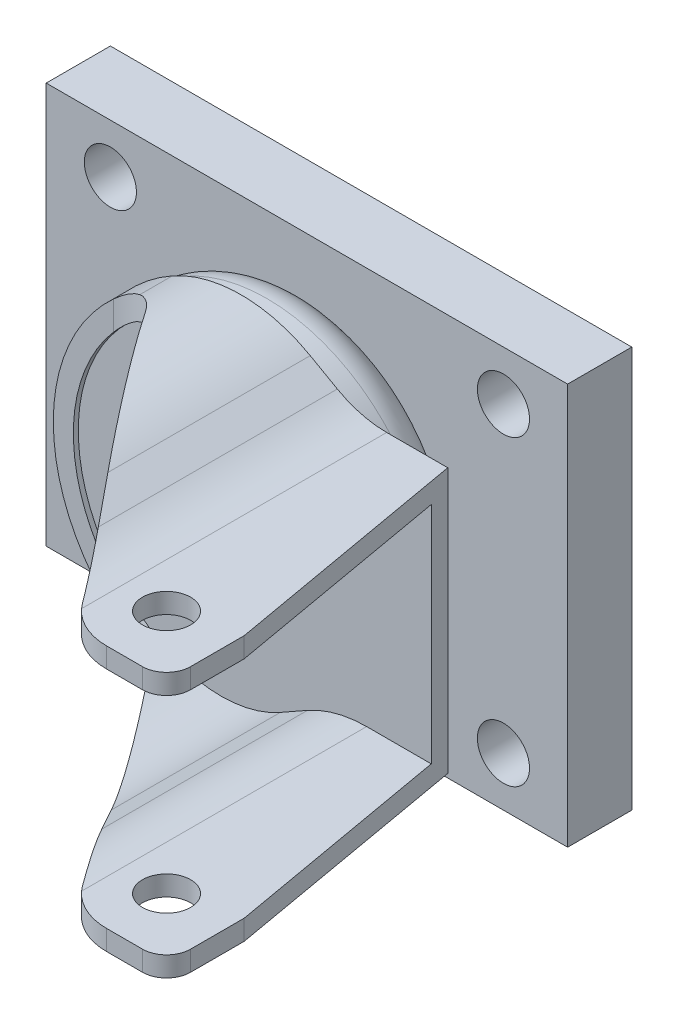
SolidWorks part; units mm, degrees
ref_plane "前视基准面" through (0, 0, 0) normal (0, 0, 1) x (1, 0, 0)
ref_plane "上视基准面" through (0, 0, 0) normal (0, 1, 0) x (1, 0, 0)
ref_plane "右视基准面" through (0, 0, 0) normal (1, 0, 0) x (0, 0, -1)
sketch "草图1" plane through (0, 0, 0) normal (0, 0, 1) x (1, 0, 0)
  line L0 (35.9458, 14) -> (49, 14)
  line L1 (35.9458, -14) -> (49, -14)
  line L2 (25.1846, 17.8522) -> (28.5649, 15.9416)
  line L3 (49, 14) -> (49, -14)
  line L4 (35.9458, -14) -> (49, -14)
  line L5 (25.1846, -17.8522) -> (28.5649, -15.9416)
  line L6 (35.9458, 14) -> (46.0599, 14)
  line L7 (35.9458, -14) -> (46.0599, -14)
  line L8 (35.9458, 14) -> (49, 14)
  line L9 (35.9458, -14) -> (49, -14)
  line L10 (25.1846, 17.8522) -> (28.5649, 15.9416)
  line L11 (49, 14) -> (49, -14)
  line L12 (35.9458, -14) -> (49, -14)
  line L13 (25.1846, -17.8522) -> (28.5649, -15.9416)
  line L14 (35.9458, 14) -> (46.0599, 14)
  line L15 (35.9458, -14) -> (46.0599, -14)
  arc A0 (10.4502, 17.8676) -> (10.4502, -17.8676) centre (20.5, 0) ccw
  arc A1 (25.1846, 17.8522) -> (10.4502, 17.8676) centre (17.8037, 4.7938) ccw
  arc A2 (28.5649, 15.9416) -> (35.9458, 14) centre (35.9458, 29) ccw
  arc A3 (10.4502, -17.8676) -> (25.1846, -17.8522) centre (17.8037, -4.7938) ccw
  arc A4 (35.9458, -14) -> (28.5649, -15.9416) centre (35.9458, -29) ccw
  arc A5 (10.4502, 17.8676) -> (10.4502, -17.8676) centre (20.5, 0) ccw
  arc A6 (25.1846, 17.8522) -> (10.4502, 17.8676) centre (17.8037, 4.7938) ccw
  arc A7 (28.5649, 15.9416) -> (35.9458, 14) centre (35.9458, 29) ccw
  arc A8 (10.4502, -17.8676) -> (25.1846, -17.8522) centre (17.8037, -4.7938) ccw
  arc A9 (35.9458, -14) -> (28.5649, -15.9416) centre (35.9458, -29) ccw
extrude "凸台-拉伸1" add sketch "草图1" along normal blind 46.5 contours A4 L1 L4 L3 L0 A2 L2 A1 A0 A3 L5 region at (24.4054, 0, 0)
sketch "草图4" plane through (0, -14, 0) normal (0, -1, 0) x (1, 0, 0)
  line L0 (49, 36.8137) -> (44, 8.5)
  line L1 (0, 8.5) -> (0, 9.114)
  line L2 (0, 9.114) -> (5, 9.114)
  line L3 (35.4725, 43.4631) -> (13.0367, 13.1632)
  line L4 (0, 8.5) -> (44, 8.5)
  line L5 (0, 46.5) -> (0, 0) construction
  line L6 (41.5, 46.5) -> (49, 46.5)
  line L7 (49, 46.5) -> (49, 0) construction
  line L8 (35.9458, 46.5) -> (49, 46.5) construction
  line L9 (49, 46.5) -> (49, 36.8137)
  arc A0 (41.5, 46.5) -> (35.4725, 43.4631) centre (41.5, 39) ccw
  arc A1 (13.0367, 13.1632) -> (5, 9.114) centre (5, 19.114) cw
  circle A4 centre (41.5, 39) radius 3
  dimension "D1" = 38
  dimension "D2" = 30.5
  dimension "D5" = 6
  dimension "D6" = 10
  dimension "D3" = 5
extrude "切除-拉伸1" cut sketch "草图4" against normal mid plane 100 flip side to cut contours L4 L0 L9 L6 A0 L3 A1 L2 L1
shell "抽壳1" thickness 2.5 removed face at (49, 0, 41.6568) removed face at (37.5527, 0.0012, 44.8635) removed face at (25.5663, 0, 30.0846) removed face at (9.5473, -0.1903, 10.8419) removed face at (2.5, 0, 9.114) removed face at (45.25, 0, 46.5) removed face at (46.5, 0, 22.6568) outward yes
sketch "草图5" plane through (0, 0, 6) normal (0, 0, -1) x (-1, 0, 0)
  line L0 (2.5, 0) -> (-49, 0) construction
  line L1 (-49, 14) -> (-49, -14) construction
  circle A0 centre (-18, 0) radius 20.5
  dimension "D1" = 41
extrude "凸台-拉伸3" add sketch "草图5" along normal blind 8
fillet "圆角1" radius 5 1 edges at (-2.5, 0, -2)
sketch "草图7" plane through (0, 0, -2) normal (0, 0, -1) x (-1, 0, 0)
  line L1 (-10, 0) -> (-14, 6.9282)
  line L2 (-14, 6.9282) -> (-22, 6.9282)
  line L3 (-22, 6.9282) -> (-26, 0)
  line L4 (-26, 0) -> (-22, -6.9282)
  line L5 (-22, -6.9282) -> (-14, -6.9282)
  line L6 (-14, -6.9282) -> (-10, 0)
  circle A0 centre (-18, 0) radius 8 construction
  dimension "D1" = 16
sketch "草图6" plane through (0, 0, -2) normal (0, 0, -1) x (-1, 0, 0)
  circle A0 centre (-18, 0) radius 5
  dimension "D1" = 10
extrude "切除-拉伸3" cut sketch "草图4<8>" against normal mid plane 96 contours A4
sketch "草图4<8>" plane through (0, -14, 0) normal (0, -1, 0) x (1, 0, 0) same geometry as "草图4"
fillet "圆角3" radius 3 2 edges at (49, 15.25, 46.5) (49, -15.25, 46.5)
sketch "草图8" plane through (0, 0, -2) normal (0, 0, -1) x (-1, 0, 0)
  line L1 (-50.5, -25) -> (14.5, -25)
  line L2 (-50.5, -25) -> (-50.5, 25)
  line L3 (-50.5, 25) -> (14.5, 25)
  line L4 (14.5, -25) -> (14.5, 25)
  line L5 (-50.5, -25) -> (14.5, 25) construction
  line L6 (-50.5, 25) -> (14.5, -25) construction
  circle A0 centre (6.5, 18.8462) radius 3.25
  circle A1 centre (6.5, -18.8462) radius 3.25
  circle A2 centre (-42.5, -18.8462) radius 3.25
  circle A3 centre (-42.5, 18.8462) radius 3.25
  point P0 (-18, 0)
  point P16 (9.4763, -25.6541)
  dimension "D7" = 6.5
  dimension "D1" = 65
  dimension "D2" = 50
  dimension "D3" = 8
  dimension "D4" = 8
  dimension "D5" = 8
  dimension "D6" = 8
extrude "凸台-拉伸4" add sketch "草图8" along normal blind 8
